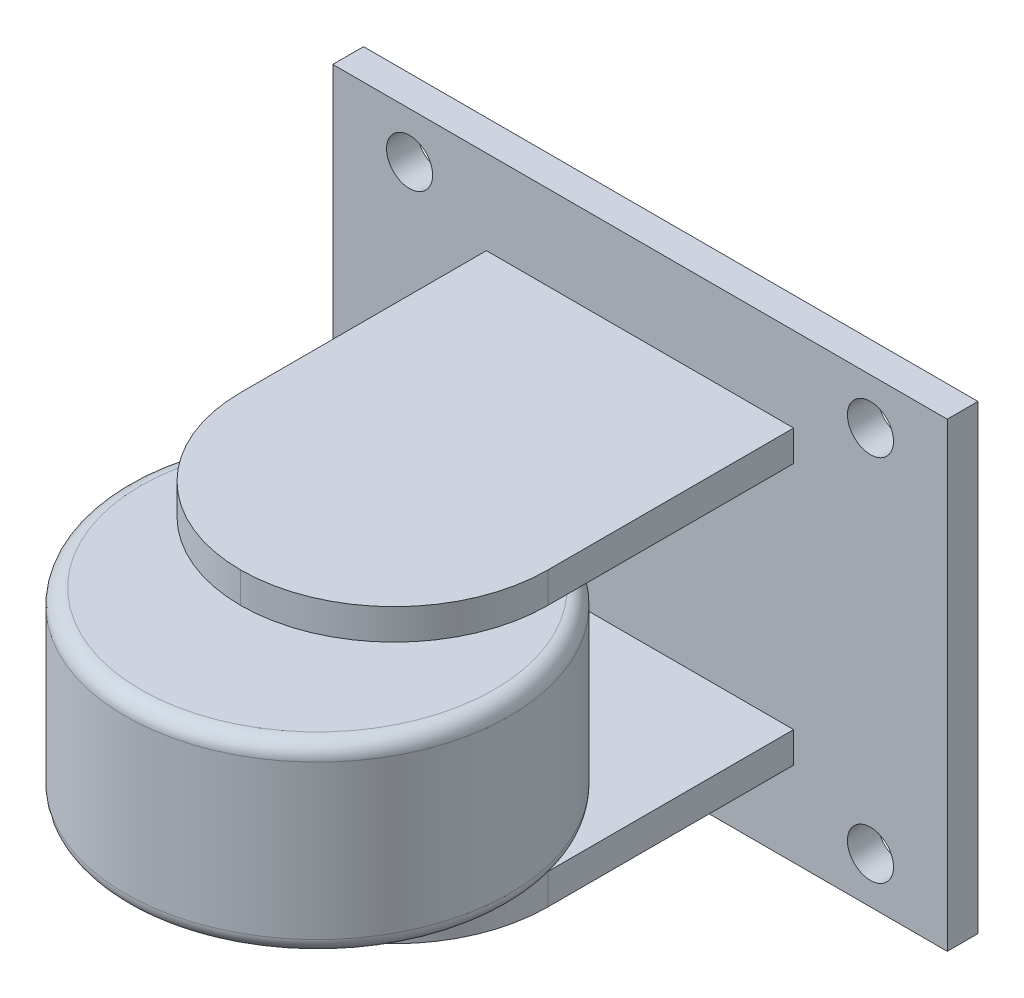
SolidWorks part; units mm, degrees
ref_plane "Front Plane" through (0, 0, 0) normal (0, 0, 1) x (1, 0, 0)
ref_plane "Top Plane" through (0, 0, 0) normal (0, 1, 0) x (1, 0, 0)
ref_plane "Right Plane" through (0, 0, 0) normal (1, 0, 0) x (0, 0, -1)
sketch "Sketch1" plane through (0, 0, 0) normal (0, 0, 1) x (1, 0, 0)
  line L1 (-20, -15) -> (20, -15)
  line L2 (-20, -15) -> (-20, 15)
  line L3 (-20, 15) -> (20, 15)
  line L4 (20, -15) -> (20, 15)
  line L5 (-20, -15) -> (20, 15) construction
  line L6 (-20, 15) -> (20, -15) construction
  point P0 (0, 0)
  dimension "D1" = 40
  dimension "D2" = 30
extrude "Boss-Extrude1" add sketch "Sketch1" along normal blind 2
sketch "Sketch2" plane through (0, 0, 2) normal (0, 0, 1) x (1, 0, 0)
  line L1 (-15, 12) -> (15, 12) construction
  line L2 (-15, 12) -> (-15, -12) construction
  line L3 (-15, -12) -> (15, -12) construction
  line L4 (15, 12) -> (15, -12) construction
  line L5 (-15, 12) -> (15, -12) construction
  line L6 (-15, -12) -> (15, 12) construction
  circle A0 centre (-15, 12) radius 1.5
  circle A1 centre (15, 12) radius 1.5
  circle A2 centre (15, -12) radius 1.5
  circle A3 centre (-15, -12) radius 1.5
  point P0 (0, 0)
  dimension "D1" = 3
  dimension "D2" = 30
  dimension "D3" = 24
extrude "Cut-Extrude1" cut sketch "Sketch2" against normal through all
sketch "Sketch3" plane through (0, 0, 2) normal (0, 0, 1) x (1, 0, 0)
  line L0 (0, 7.5) -> (0, -7.5) construction
  line L1 (-10, -7.5) -> (10, -7.5)
  line L2 (-10, -7.5) -> (-10, -9.5)
  line L3 (-10, -9.5) -> (10, -9.5)
  line L4 (10, -7.5) -> (10, -9.5)
  line L5 (10, 7.5) -> (-10, 7.5)
  line L6 (10, 7.5) -> (10, 9.5)
  line L7 (10, 9.5) -> (-10, 9.5)
  line L8 (-10, 7.5) -> (-10, 9.5)
  point P10 (0, 0)
  dimension "D1" = 20
  dimension "D2" = 2
  dimension "D3" = 15
extrude "Boss-Extrude2" add sketch "Sketch3" along normal blind 26
sketch "Sketch4" plane through (0, 9.5, 0) normal (0, 1, 0) x (1, 0, 0)
  line L0 (20, 0) -> (-20, 0) construction
  line L1 (10, -28) -> (-10, -28) construction
  circle A0 centre (0, -23) radius 2.5
  point P7 (0, -28)
  dimension "D2" = 5
  dimension "D1" = 23
extrude "Boss-Extrude3" add sketch "Sketch4" against normal up to surface (19 mm away) up to face at (0, -9.5, 15)
ref_plane "Plane1" through (0, 0, 0) normal (0, -1, 0) x (-1, 0, 0)
sketch "Sketch5" plane through (0, 0, 0) normal (0, -1, 0) x (-1, 0, 0)
  circle A0 centre (0, -23) radius 12.5
  circle A1 centre (0, -23) radius 2.5 construction
  dimension "D1" = 25
extrude "Boss-Extrude4" add sketch "Sketch5" against normal blind 6 and the other way blind 6
fillet "Fillet1" radius 10 4 edges at (10, -8.5, 28) (-10, -8.5, 28) (10, 8.5, 28) (-10, 8.5, 28)
fillet "Fillet2" radius 1 2 edges at (0, -6, 10.5) (0, 6, 10.5)
